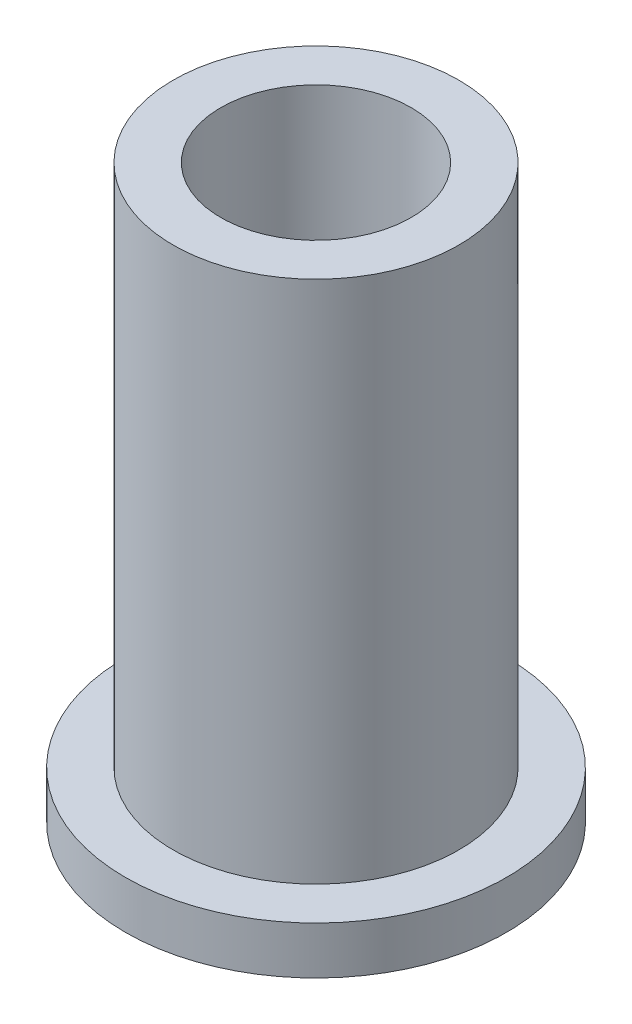
SolidWorks part; units mm, degrees
material "Brass"
ref_plane "Front Plane" through (0, 0, 0) normal (0, 0, 1) x (1, 0, 0)
ref_plane "Top Plane" through (0, 0, 0) normal (0, 1, 0) x (1, 0, 0)
ref_plane "Right Plane" through (0, 0, 0) normal (1, 0, 0) x (0, 0, -1)
sketch "Sketch1" plane through (0, 0, 0) normal (0, 0, 1) x (1, 0, 0)
  line L0 (3.175, 0) -> (6.35, 0)
  line L1 (6.35, 0) -> (6.35, 1.5875)
  line L2 (6.35, 1.5875) -> (4.7625, 1.5875)
  line L3 (4.7625, 1.5875) -> (4.7625, 19.05)
  line L4 (4.7625, 19.05) -> (3.175, 19.05)
  line L5 (3.175, 19.05) -> (3.175, 0)
  line L6 (0, 0) -> (0, 40.9931) construction
  dimension "D1" = 6.35
  dimension "D2" = 9.525
  dimension "D3" = 12.7
  dimension "D4" = 1.5875
  dimension "D5" = 19.05
revolve "Revolve1" add sketch "Sketch1" angle 360 about L6
